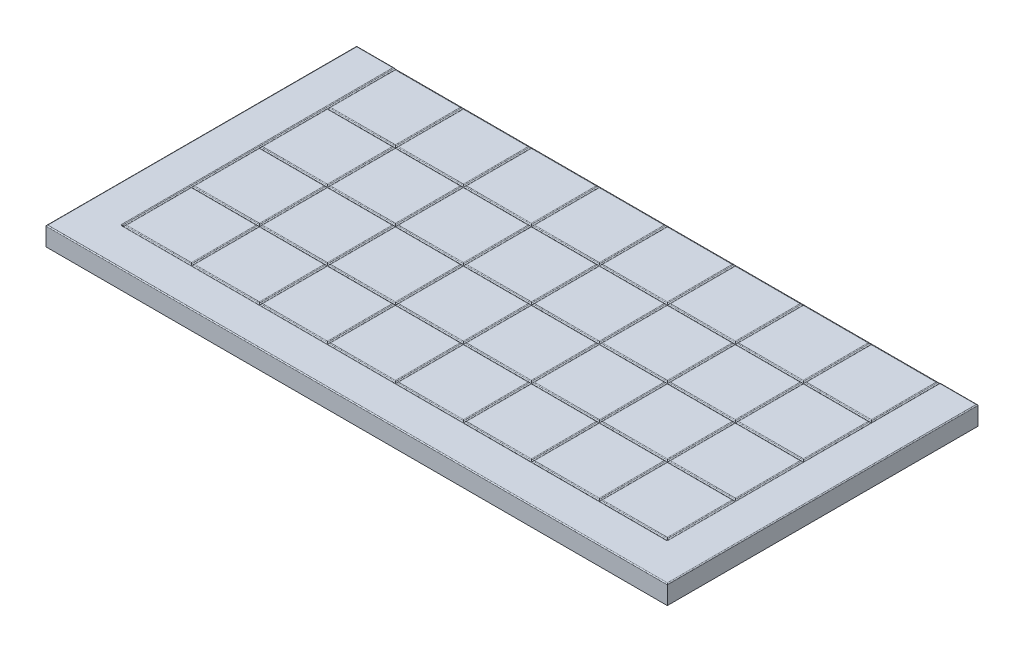
SolidWorks part; units mm, degrees
ref_plane "Спереди" through (0, 0, 0) normal (0, 0, 1) x (1, 0, 0)
ref_plane "Сверху" through (0, 0, 0) normal (0, 1, 0) x (1, 0, 0)
ref_plane "Справа" through (0, 0, 0) normal (1, 0, 0) x (0, 0, -1)
sketch "Эскиз1" plane through (0, 0, 0) normal (0, 1, 0) x (1, 0, 0)
  line L135 (0, 273.8386) -> (0, -311.6512) construction
  line L143 (0, 144) -> (0, 0) construction
  line L275 (-144, 164.5) -> (144, 164.5)
  line L283 (164.5, 164.5) -> (144, 164.5)
  line L284 (164.5, 164.5) -> (164.5, 0)
  line L285 (164.5, 0) -> (-164.5, 0)
  line L286 (-164.5, 164.5) -> (-164.5, 0)
  line L287 (-144, 164.5) -> (-164.5, 164.5)
  point P31 (0, 0)
  dimension "D1" = 329
  dimension "D2" = 164.5
  dimension "D5" = 20.5
extrude "Бобышка-Вытянуть1" add sketch "Эскиз1" against normal blind 10
sketch "Эскиз2" plane through (0, 0, 0) normal (0, 1, 0) x (1, 0, 0)
  line L0 (-144, 164.5) -> (-144, 20.5)
  line L1 (164.5, 164.5) -> (-164.5, 164.5) construction
  line L10 (-164.5, 164.5) -> (-164.5, 0) construction
  dimension "D2" = 20.5
  dimension "D3" = 144
sweep "Вырез-По траектории1" cut path "Эскиз2" circular profile diameter 1 parameters "D3"=1
pattern_linear "Линейный массив1" count 9 spacing 36 along (1, 0, 0) of "Вырез-По траектории1"
sketch "Эскиз28" plane through (0, 0, 0) normal (0, 1, 0) x (1, 0, 0)
  line L0 (-144, 20.5) -> (144, 20.5)
  line L1 (164.5, 0) -> (164.5, 164.5) construction
  dimension "D1" = 288
  dimension "D2" = 20.5
sweep "Вырез-По траектории2" cut path "Эскиз28" circular profile diameter 1 parameters "D3"=1
pattern_linear "Линейный массив7" count 5 spacing 36 along (0, 0, -1) of "Вырез-По траектории2"
fillet "Скругление3" radius 0.5 140 edges at (-108.5, 0, -146.5) (-126, 0, -129) (-143.5, 0, -146.5) (-126, 0, -164) (-72.5, 0, -146.5) (-90, 0, -129) (-107.5, 0, -146.5) (-90, 0, -164) (-36.5, 0, -146.5) (-54, 0, -129) (-71.5, 0, -146.5) (-54, 0, -164) (-0.5, 0, -146.5) (-18, 0, -129) (-35.5, 0, -146.5) (-18, 0, -164) (71.5, 0, -146.5) (54, 0, -129) (36.5, 0, -146.5) (54, 0, -164) (35.5, 0, -146.5) (18, 0, -129) (0.5, 0, -146.5) (18, 0, -164) (35.5, 0, -110.5) (18, 0, -93) (0.5, 0, -110.5) (18, 0, -128) (-0.5, 0, -110.5) (-18, 0, -93) (-35.5, 0, -110.5) (-18, 0, -128) (-36.5, 0, -110.5) (-54, 0, -93) (-71.5, 0, -110.5) (-54, 0, -128) (-72.5, 0, -110.5) (-90, 0, -93) (-107.5, 0, -110.5) (-90, 0, -128) (-72.5, 0, -74.5) (-90, 0, -57) (-107.5, 0, -74.5) (-90, 0, -92) (-36.5, 0, -74.5) (-54, 0, -57) (-71.5, 0, -74.5) (-54, 0, -92) (-0.5, 0, -74.5) (-18, 0, -57) (-35.5, 0, -74.5) (-18, 0, -92) (35.5, 0, -74.5) (18, 0, -57) (0.5, 0, -74.5) (18, 0, -92) (107.5, 0, -74.5) (90, 0, -57) (72.5, 0, -74.5) (90, 0, -92) (71.5, 0, -74.5) (54, 0, -57) (36.5, 0, -74.5) (54, 0, -92) (71.5, 0, -110.5) (54, 0, -93) (36.5, 0, -110.5) (54, 0, -128) (107.5, 0, -110.5) (90, 0, -93) (72.5, 0, -110.5) (90, 0, -128) (107.5, 0, -146.5) (90, 0, -129) (72.5, 0, -146.5) (90, 0, -164) (143.5, 0, -146.5) (126, 0, -129) (108.5, 0, -146.5) (126, 0, -164) (143.5, 0, -110.5) (126, 0, -93) (108.5, 0, -110.5) (126, 0, -128) (143.5, 0, -74.5) (126, 0, -57) (108.5, 0, -74.5) (126, 0, -92) (143.5, 0, -38.5) (126, 0, -21) (108.5, 0, -38.5) (126, 0, -56) (107.5, 0, -38.5) (90, 0, -21) (72.5, 0, -38.5) (90, 0, -56) (71.5, 0, -38.5) (54, 0, -21) (36.5, 0, -38.5) (54, 0, -56) (35.5, 0, -38.5) (18, 0, -21) (0.5, 0, -38.5) (18, 0, -56) (-0.5, 0, -38.5) (-18, 0, -21) (-35.5, 0, -38.5) (-18, 0, -56) (-36.5, 0, -38.5) (-54, 0, -21) (-71.5, 0, -38.5) (-54, 0, -56) (-72.5, 0, -38.5) (-90, 0, -21) (-107.5, 0, -38.5) (-90, 0, -56) (-108.5, 0, -38.5) (-126, 0, -21) (-143.5, 0, -38.5) (-126, 0, -56) (144, 0, -20.25) (144.25, 0, -20.5) (144.5, 0, -92.5) (154.5, 0, -164.5) (164.5, 0, -82.25) (0, 0, 0) (-164.5, 0, -82.25) (-154.5, 0, -164.5) (-144.5, 0, -92.5) (-144.25, 0, -20.5) (-144, 0, -20.25) (0, 0, -20) (-108.5, 0, -110.5) (-126, 0, -93) (-143.5, 0, -110.5) (-126, 0, -128) (-108.5, 0, -74.5) (-126, 0, -57) (-143.5, 0, -74.5) (-126, 0, -92)
